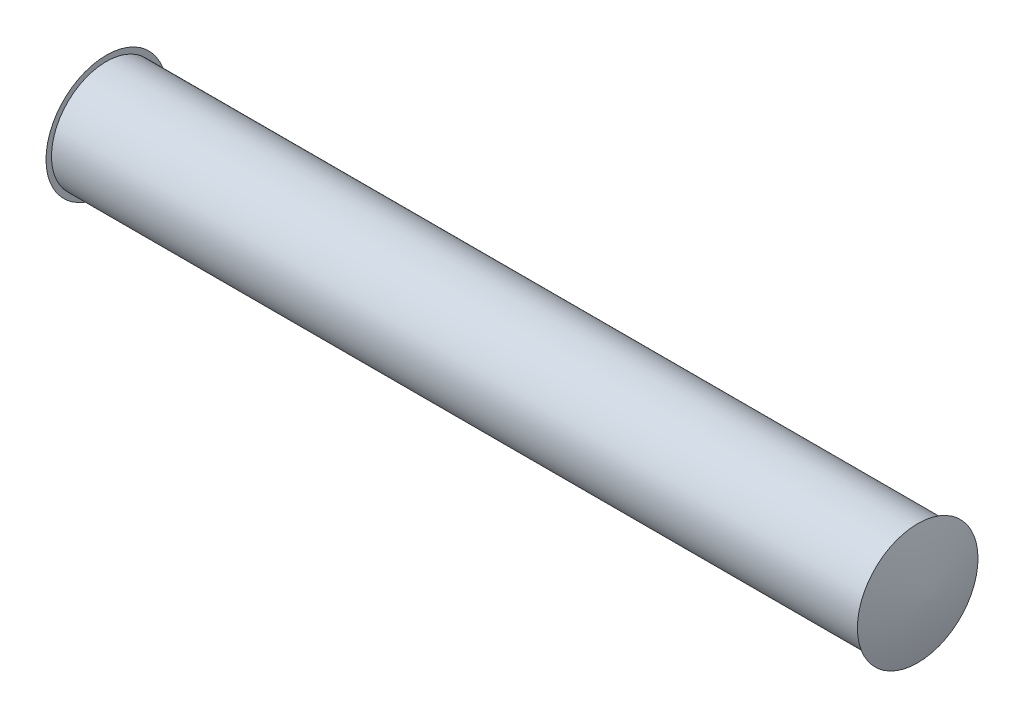
SolidWorks part; units mm, degrees
material "Cast Alloy Steel"
ref_plane "Front Plane" through (0, 0, 0) normal (0, 0, 1) x (1, 0, 0)
ref_plane "Top Plane" through (0, 0, 0) normal (0, 1, 0) x (1, 0, 0)
ref_plane "Right Plane" through (0, 0, 0) normal (1, 0, 0) x (0, 0, -1)
sketch "Sketch1" plane through (0, 0, 0) normal (1, 0, 0) x (0, 0, -1)
  circle A0 centre (0, 0) radius 1.27
  dimension "D1" = 2.54
extrude "Boss-Extrude1" add sketch "Sketch1" along normal blind 9.398 and the other way blind 9.398
sketch "Sketch5" plane through (0, 0, 0) normal (0, 1, 0) x (1, 0, 0)
  line L0 (9.398, 0) -> (9.398, 1.397)
  line L1 (9.398, -1.27) -> (9.398, 1.27) construction
  line L2 (9.398, 0) -> (9.652, 0)
  line L3 (9.652, 0) -> (9.652, -2.1779) construction
  line L4 (9.398, 1.397) -> (7.9267, 1.397) construction
  spline S0 degree 2 poles (9.398, 1.397) (9.6131, 0.7147) (9.652, 0) knots 0 0 0 1 1 1
  dimension "D1" = 1.397
  dimension "D2" = 0.254
revolve "Revolve1" add sketch "Sketch5" angle 360 about L2
mirror "Mirror1" about plane through (0, 0, 0) normal (1, 0, 0) of "Revolve1"
